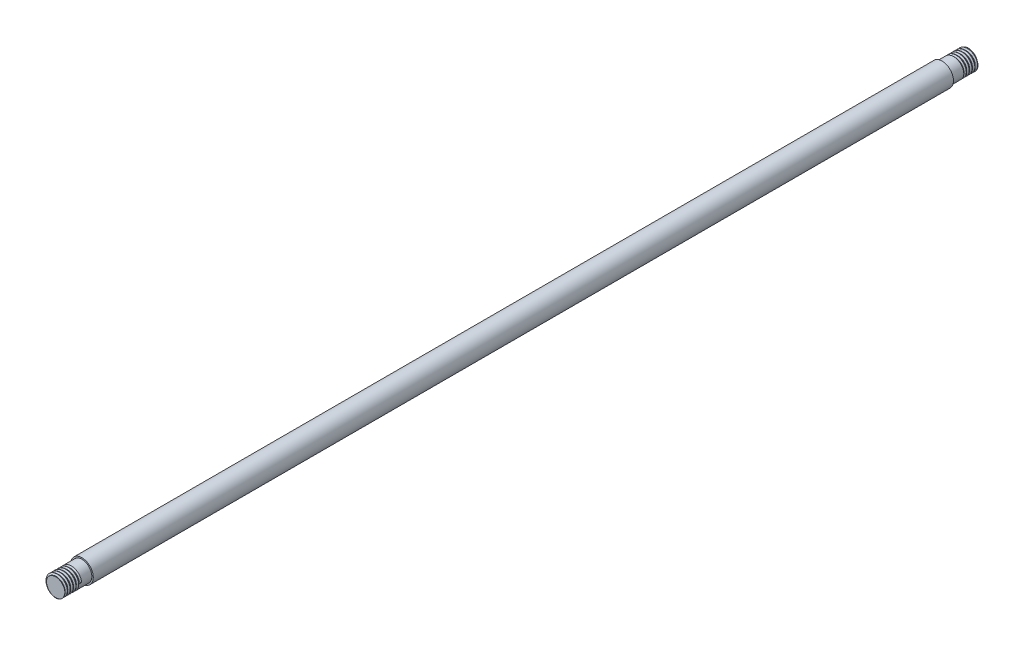
SolidWorks part; units mm, degrees
ref_plane "Front Plane" through (0, 0, 0) normal (0, 0, 1) x (1, 0, 0)
ref_plane "Top Plane" through (0, 0, 0) normal (0, 1, 0) x (1, 0, 0)
ref_plane "Right Plane" through (0, 0, 0) normal (1, 0, 0) x (0, 0, -1)
sketch "Sketch1" plane through (0, 0, 0) normal (1, 0, 0) x (0, 0, -1)
  line L27 (-69.0229, 0) -> (573.9771, 0)
  line L28 (573.9771, 0) -> (573.9771, -7)
  line L29 (573.9771, -7) -> (554.9771, -7)
  line L30 (554.9771, -7) -> (554.9771, -8)
  line L31 (554.9771, -8) -> (-50.0229, -8)
  line L32 (-50.0229, -8) -> (-50.0229, -7)
  line L33 (-50.0229, -7) -> (-69.0229, -7)
  line L34 (-69.0229, -7) -> (-69.0229, 0)
  dimension "D1" = 643
  dimension "D2" = 19
  dimension "D3" = 19
  dimension "D4" = 7
  dimension "D5" = 8
  dimension "D6" = 7
revolve "Revolve8" add sketch "Sketch1" angle 360 about L27
thread "Thread1" pitch 2 start angle 0, offset 3, length 10, pitch 2, diameter 14
ref_plane "Plane1" through (-7, 0, 72.0229) normal (0, -1, 0) x (-1, 0, 0)
sketch "Thread Profile1" plane through (-7, 0, 72.0229) normal (0, -1, 0) x (-1, 0, 0)
  line L0 (0, 0) -> (0, 2) construction
  line L11 (0, 0) -> (0, 1.75)
  line L12 (0, 1.75) -> (-1.0825, 1.125)
  line L13 (-1.0825, 1.125) -> (-1.0825, 0.625)
  line L15 (-1.0825, 0.625) -> (0, 0)
  line L17 (-1.0825, 0.875) -> (0, 0.875) construction
  point P2 (0, 0)
  dimension "Pitch" = 2
  dimension "Profile_Angle" = 60
  dimension "Profile_Land" = 0.5
  dimension "Profile_Height" = 1.0825
thread "Thread2" pitch 2 profile "Thread Profile2" start angle 0, offset 3, length 10, pitch 2, diameter 14
ref_plane "Plane2" through (7, 0, -576.9771) normal (0, -1, 0) x (1, 0, 0)
sketch "Thread Profile2" plane through (7, 0, -576.9771) normal (0, -1, 0) x (1, 0, 0)
  line L0 (0, 0) -> (0, 2) construction
  line L11 (0, 0) -> (0, 1.75)
  line L12 (0, 1.75) -> (-1.0825, 1.125)
  line L13 (-1.0825, 1.125) -> (-1.0825, 0.625)
  line L15 (-1.0825, 0.625) -> (0, 0)
  line L17 (-1.0825, 0.875) -> (0, 0.875) construction
  point P2 (0, 0)
  dimension "Pitch" = 2
  dimension "Profile_Angle" = 60
  dimension "Profile_Land" = 0.5
  dimension "Profile_Height" = 1.0825
